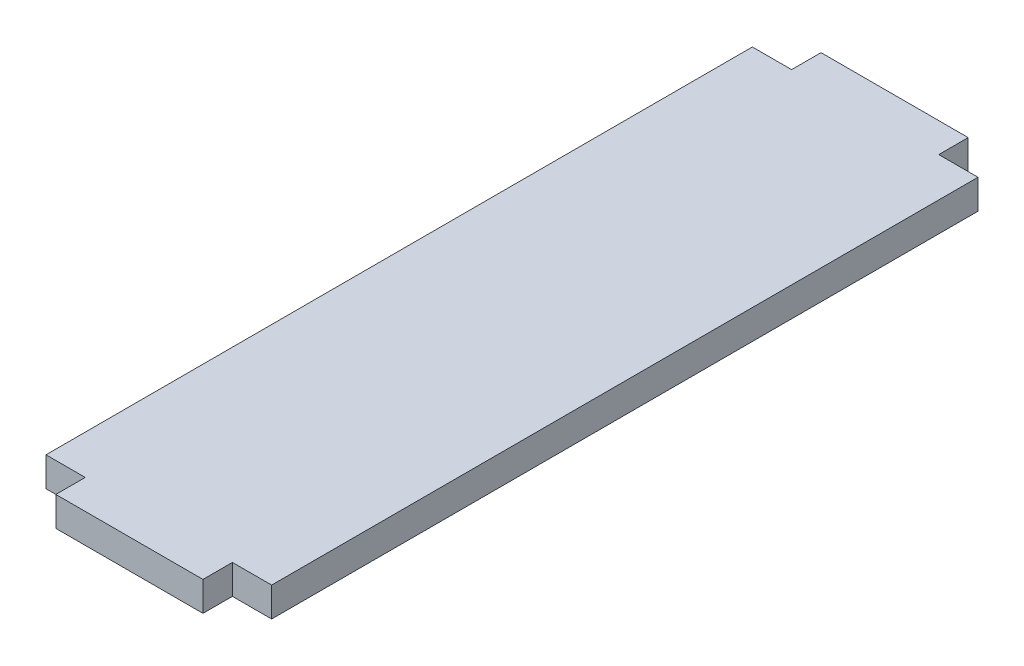
SolidWorks part; units mm, degrees
material "AISI 304"
ref_plane "Front Plane" through (0, 0, 0) normal (0, 0, 1) x (1, 0, 0)
ref_plane "Top Plane" through (0, 0, 0) normal (0, 1, 0) x (1, 0, 0)
ref_plane "Right Plane" through (0, 0, 0) normal (1, 0, 0) x (0, 0, -1)
sketch "Sketch1" plane through (0, 0, 0) normal (0, 1, 0) x (1, 0, 0)
  line L0 (3.75, 18) -> (5.75, 18)
  line L1 (-5.75, -18) -> (-3.75, -18)
  line L2 (-5.75, -18) -> (-5.75, 18)
  line L3 (-5.75, 18) -> (-3.75, 18)
  line L4 (5.75, -18) -> (5.75, 18)
  line L5 (-5.75, -18) -> (5.75, 18) construction
  line L6 (-5.75, 18) -> (5.75, -18) construction
  line L8 (-3.75, 18) -> (-3.75, 19.5)
  line L9 (-3.75, 19.5) -> (3.75, 19.5)
  line L10 (3.75, 18) -> (3.75, 19.5)
  line L12 (-3.75, -18) -> (-3.75, -19.5)
  line L13 (-3.75, -19.5) -> (3.75, -19.5)
  line L14 (3.75, -18) -> (3.75, -19.5)
  line L15 (3.75, -18) -> (5.75, -18)
  point P0 (0, 0)
  dimension "D1" = 2
  dimension "D2" = 2
  dimension "D3" = 7.5
  dimension "D4" = 2
  dimension "D5" = 2
  dimension "D6" = 1.5
  dimension "D7" = 1.5
  dimension "D8" = 36
extrude "Boss-Extrude1" add sketch "Sketch1" along normal blind 1.5
